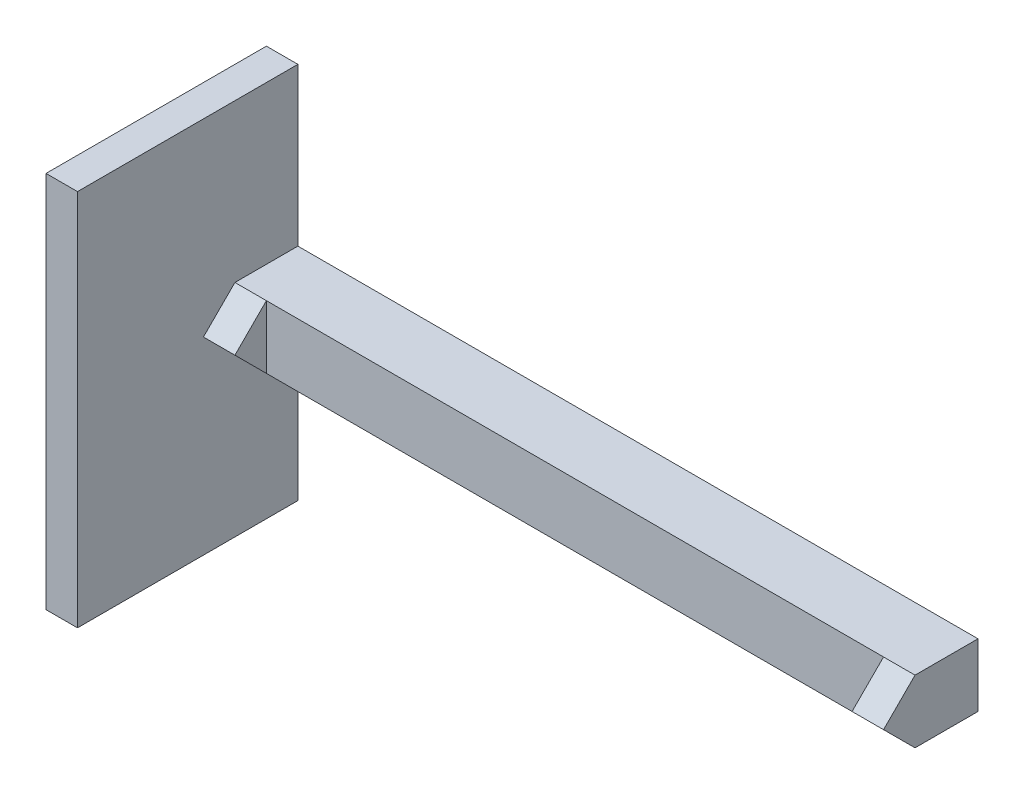
SolidWorks part; units mm, degrees
ref_plane "Front Plane" through (0, 0, 0) normal (1, 0, 0) x (0, 1, 0)
ref_plane "Top Plane" through (0, 0, 0) normal (0, 0, 1) x (0, 1, 0)
ref_plane "Right Plane" through (0, 0, 0) normal (0, 1, 0) x (-1, 0, 0)
ref_axis "x axis" through (-88.99, 0, 0) along (1, 0, 0)
ref_axis "y xxis" through (0, 88.99, 0) along (0, -1, 0)
ref_axis "z axis" through (0, 0, 55) along (0, 0, -1)
sketch "Sketch1" plane through (0, 0, 0) normal (0, 0, 1) x (0, 1, 0)
  line L1 (-5, -56.5) -> (5, -56.5)
  line L2 (-5, -56.5) -> (-5, 56.5)
  line L3 (-5, 56.5) -> (5, 56.5)
  line L4 (5, -56.5) -> (5, 56.5)
  line L5 (-5, -56.5) -> (5, 56.5) construction
  line L6 (-5, 56.5) -> (5, -56.5) construction
  point P0 (0, 0)
  dimension "D1" = 10
  dimension "D2" = 113
extrude "Boss-Extrude1" add sketch "Sketch1" along normal blind 10
sketch "Sketch3" plane through (56.5, 0, 0) normal (1, 0, 0) x (0, 1, 0)
  line L0 (-5, 10) -> (0, 15)
  line L2 (0, 15) -> (5, 10)
  line L3 (0, 15) -> (0, 10) construction
  line L4 (-5, 10) -> (5, 10) construction
  line L5 (-5, 10) -> (5, 10)
  point P1 (0.0178, 15)
  point P10 (-0.0215, 15)
  dimension "D2" = 5
extrude "Boss-Extrude2" add sketch "Sketch3" against normal blind 5
sketch "Sketch4" plane through (-56.5, 0, 0) normal (-1, 0, 0) x (0, -1, 0)
  line L1 (-30, 0) -> (30, 0)
  line L2 (-30, 0) -> (-30, 35)
  line L3 (-30, 35) -> (30, 35)
  line L4 (30, 0) -> (30, 35)
  point P4 (0, 0)
  dimension "D1" = 60
  dimension "D2" = 20
extrude "Boss-Extrude3" add sketch "Sketch4" against normal blind 5
sketch "Sketch5" plane through (-51.5, 0, 0) normal (1, 0, 0) x (0, 1, 0)
  line L0 (5, 10) -> (0, 15)
  line L1 (5, 10) -> (0, 15) construction
  line L2 (0, 15) -> (-5, 10)
  line L3 (-5, 10) -> (5, 10)
  point P5 (-5, 10)
extrude "Boss-Extrude4" add sketch "Sketch5" along normal blind 5
